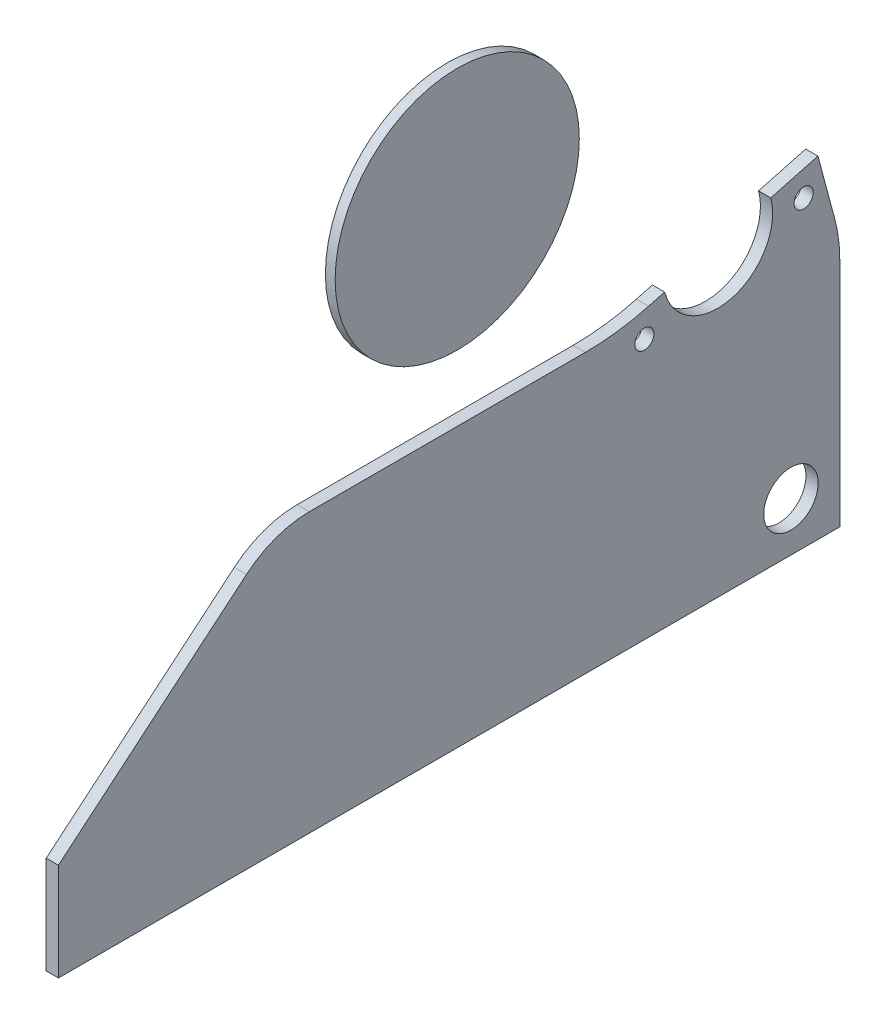
SolidWorks part; units mm, degrees
material "6061-T6 (SS)"
ref_plane "Front Plane" through (0, 0, 0) normal (0, 0, 1) x (1, 0, 0)
ref_plane "Top Plane" through (0, 0, 0) normal (0, 1, 0) x (1, 0, 0)
ref_plane "Right Plane" through (0, 0, 0) normal (1, 0, 0) x (0, 0, -1)
sketch "Sketch1" plane through (0, 0, 0) normal (1, 0, 0) x (0, 0, -1)
  line L0 (0, -25.4) -> (0, 39.7541)
  line L7 (-5.6821, 60.9599) -> (-17.9493, 57.6729)
  line L8 (-45.5507, 50.2771) -> (-57.8179, 46.9901)
  line L10 (-57.8179, 46.9901) -> (-137.9545, 46.9901)
  line L13 (-203.2, -25.4) -> (0, -25.4)
  line L14 (-203.2, -25.4) -> (-203.2, 0)
  line L15 (-203.2, 0) -> (-154.2813, 41.0476)
  line L16 (-203.2, 0) -> (0, 0) construction
  line L17 (-5.6821, 60.9599) -> (0, 39.7541)
  arc A2 (-17.9493, 57.6729) -> (-45.5507, 50.2771) centre (-31.75, 53.975) cw
  arc A4 (-137.9545, 46.9901) -> (-154.2813, 41.0476) centre (-137.9545, 21.5901) ccw
  circle A5 centre (-31.75, 53.975) radius 12.7 construction
  point P4 (0, 0)
  dimension "D1" = 28.575
  dimension "D4" = 25.4
  dimension "D7" = 25.4
  dimension "D10" = 25.4
  dimension "D3" = 41.275
  dimension "D11" = 15
  dimension "D9" = 31.75
  dimension "D2" = 15
  dimension "D5" = 12.7
  dimension "D6" = 203.2
  dimension "D8" = 50
extrude "Boss-Extrude1" add sketch "Sketch1" along normal blind 3.175
hole_wizard "#10 Clearance Hole1" positions "Sketch2" profile "Sketch3" hole size "#10" standard "ANSI Inch" end condition through all
sketch "Sketch2" plane through (3.175, 0, 0) normal (1, 0, 0) x (0, 0, -1)
  line L0 (-45.5507, 50.2771) -> (-57.8179, 46.9901) construction
  line L1 (-50.8075, 42.2946) -> (-9.4055, 53.3882) construction
  line L3 (-30.1065, 47.8414) -> (-31.75, 53.975) construction
  line L4 (-5.6821, 60.9599) -> (-17.9493, 57.6729) construction
  point P0 (-50.8075, 42.2946)
  point P2 (-9.4055, 53.3882)
  dimension "D1" = 42.8625
  dimension "D2" = 6.35
sketch "Sketch3" plane through (3.175, 42.2946, 50.8075) normal (0, 1, 0) x (0, 0, -1)
  line L0 (0, 0) -> (0, 3.175)
  line L1 (0, 3.175) -> (2.4892, 3.175)
  line L2 (2.4892, 3.175) -> (2.4892, 0)
  line L5 (2.4892, 0) -> (0, 0)
  line L11 (0, -6.35) -> (0, 107.95) construction
  dimension "Thru Hole Dia." = 4.9784
  dimension "Thru Hole Depth" = 3.175
sketch "Sketch9" plane through (3.175, 0, 0) normal (1, 0, 0) x (0, 0, -1)
  line L2 (0, -25.4) -> (0, 39.7541) construction
  line L3 (-203.2, -25.4) -> (0, -25.4) construction
  circle A0 centre (-12.7, -12.7) radius 7.0739
  dimension "D1" = 14.1478
  dimension "D3" = 12.7
  dimension "D2" = 12.7
extrude "Cut-Extrude1" cut sketch "Sketch9" against normal through all
fillet "Fillet1" radius 38.1 1 edges at (1.5875, 39.7541, 0)
fillet "Fillet2" radius 63.5 1 edges at (1.5875, 46.9901, 57.8179)
sketch "Sketch10" plane through (0, 0, 0) normal (1, 0, 0) x (0, 0, -1)
  line L0 (-203.2, 0) -> (0, 0) construction
  circle A0 centre (-98.8508, 95.25) radius 31.75
  circle A1 centre (-98.8508, 95.25) radius 12.8927 construction
  circle A2 centre (-31.75, 53.975) radius 12.8927 construction
  dimension "D1" = 63.5
  dimension "D2" = 63.5
extrude "Boss-Extrude2" add sketch "Sketch10" along normal blind 2.54
